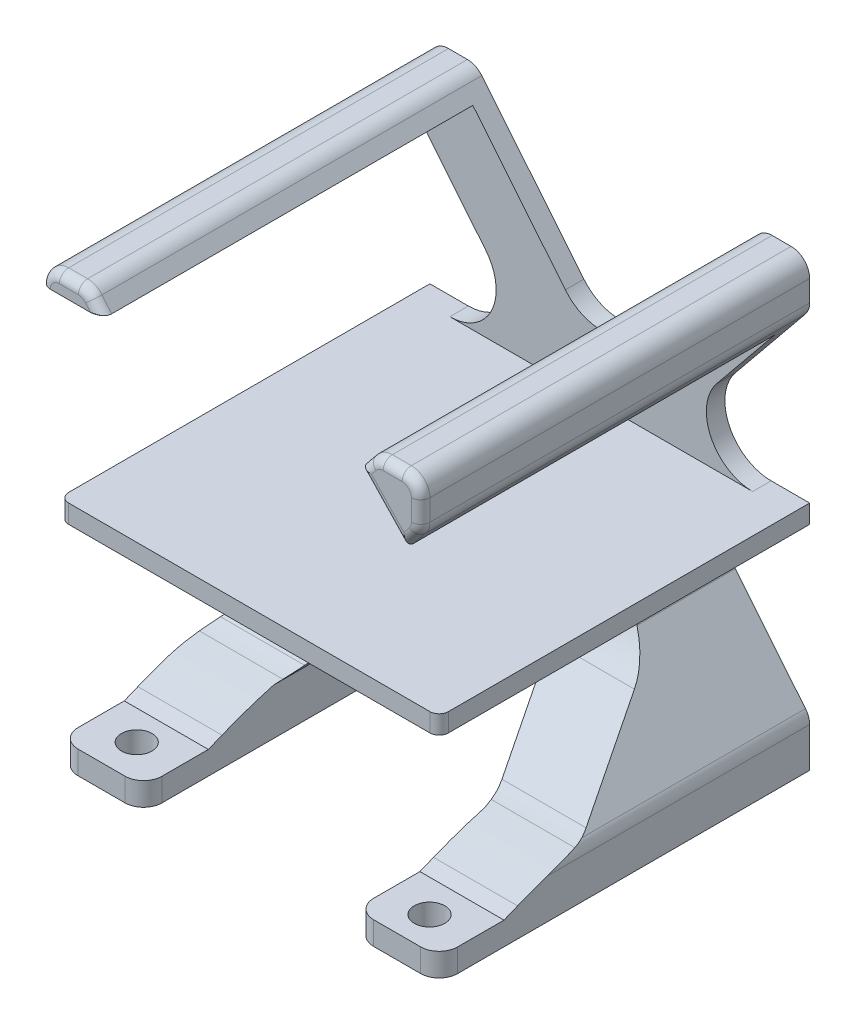
SolidWorks part; units mm, degrees
ref_plane "Front Plane" through (0, 0, 0) normal (0, 0, 1) x (1, 0, 0)
ref_plane "Top Plane" through (0, 0, 0) normal (0, 1, 0) x (1, 0, 0)
ref_plane "Right Plane" through (0, 0, 0) normal (1, 0, 0) x (0, 0, -1)
sketch "Sketch1" plane through (0, 0, 0) normal (0, 0, 1) x (1, 0, 0)
  line L0 (-20.5, -19) -> (-5.8158, -1)
  line L1 (-20.5, -24) -> (-15.5, -24)
  line L2 (-20.5, -24) -> (-20.5, -19)
  line L3 (-20.5, 24) -> (-15.5, 24)
  line L4 (20.5, -24) -> (20.5, -19)
  line L5 (20.5, 19) -> (20.5, 24)
  line L6 (20.5, -1) -> (20.5, 1)
  line L7 (-5.8158, 1) -> (-20.5, 19)
  line L8 (5.8158, 1) -> (20.5, 1)
  line L9 (-15.5, 24) -> (0, 5)
  line L10 (0, 5) -> (15.5, 24)
  line L11 (-20.5, -1) -> (-20.5, 1)
  line L12 (20.5, 19) -> (5.8158, 1)
  line L13 (5.8158, -1) -> (20.5, -19)
  line L14 (-20.5, 19) -> (-20.5, 24)
  line L15 (15.5, -24) -> (0, -5)
  line L16 (0, -5) -> (-15.5, -24)
  line L17 (15.5, 24) -> (20.5, 24)
  line L18 (-20.5, 1) -> (-5.8158, 1)
  line L20 (-20.5, -1) -> (-5.8158, -1)
  line L22 (15.5, -24) -> (20.5, -24)
  line L24 (5.8158, -1) -> (20.5, -1)
  point P0 (0, 0)
  point P5 (0, 0)
  dimension "D1" = 48
  dimension "D2" = 41
  dimension "D3" = 5
  dimension "D4" = 5
  dimension "D5" = 5
  dimension "D6" = 5
  dimension "D7" = 5
  dimension "D8" = 5
  dimension "D9" = 5
  dimension "D11" = 0
  dimension "D12" = 5
  dimension "D15" = 5
  dimension "D16" = 2
  dimension "D17" = 23
extrude "Boss-Extrude1" add sketch "Sketch1" along normal blind 40
sketch "Sketch2" plane through (0, 0, 40) normal (0, 0, 1) x (1, 0, 0)
  line L0 (-5.8158, 1) -> (-20.5, 1) construction
  line L1 (-18.75, 1) -> (18.75, 1)
  line L2 (-18.75, 1) -> (-18.75, 22)
  line L3 (-18.75, 22) -> (18.75, 22)
  line L4 (18.75, 1) -> (18.75, 22)
  line L5 (-15.5, 24) -> (-20.5, 24) construction
  dimension "D1" = 37.5
  dimension "D2" = 1.75
  dimension "D3" = 2
extrude "Cut-Extrude1" cut sketch "Sketch2" against normal blind 38
sketch "Sketch4" plane through (20.5, 0, 0) normal (1, 0, 0) x (0, 0, -1)
  line L0 (-40, -1) -> (0, -1) construction
  line L1 (-40, -19) -> (-10, -19)
  line L2 (-40, -19) -> (-40, -1)
  line L3 (-40, -1) -> (-10, -1)
  line L4 (-10, -19) -> (-10, -1)
  dimension "D1" = 30
extrude "Cut-Extrude2" cut sketch "Sketch4" against normal blind 100
chamfer "Chamfer1" distance 15 angle 30 2 edges at (-15.9605, -19, 10) (15.9605, -19, 10) first distance on face at (-15.9605, -19, 25) first distance on face at (15.9605, -19, 25)
fillet "Fillet1" radius 7 4 edges at (-15.9605, -19, 25) (15.9605, -19, 25) (0, -1, 10) (8.8956, -10.3397, 10)
sketch "Sketch5" plane through (0, 0, 40) normal (0, 0, 1) x (1, 0, 0)
  line L0 (-20.5, 24) -> (-20.5, 19)
  line L1 (-20.5, 19) -> (-18.75, 16.8548)
  line L2 (-18.75, 16.8548) -> (-13.8684, 22)
  line L3 (-13.8684, 22) -> (-15.5, 24)
  line L4 (-15.5, 24) -> (-20.5, 24)
  line L5 (13.8684, 22) -> (15.5, 24)
  line L6 (15.5, 24) -> (20.5, 24)
  line L7 (20.5, 24) -> (20.5, 19)
  line L8 (20.5, 19) -> (18.75, 16.8548)
  line L11 (13.8684, 22) -> (18.75, 16.8548)
extrude "Boss-Extrude3" add sketch "Sketch5" along normal blind 2
fillet "Fillet4" radius 2 6 edges at (-20.5, 19, 21) (-20.5, 24, 21) (-15.5, 24, 21) (15.5, 24, 21) (20.5, 19, 21) (20.5, 24, 21)
fillet "Fillet5" radius 1 16 edges at (19.9142, 23.4142, 42) (20.5, 20.8562, 42) (20.3841, 19.0413, 42) (19.3999, 17.6514, 42) (16.3092, 19.4274, 42) (14.3841, 22.6321, 42) (15.5918, 23.8067, 42) (17.4748, 24, 42) (-19.9142, 23.4142, 42) (-17.4748, 24, 42) (-15.5918, 23.8067, 42) (-14.3841, 22.6321, 42) (-16.3092, 19.4274, 42) (-19.3999, 17.6514, 42) (-20.3841, 19.0413, 42) (-20.5, 20.8562, 42)
fillet "Fillet6" radius 5 5 edges at (-5.8158, 1, 1) (-5.8158, -1, 8.5) (5.8158, -1, 8.5) (5.8158, 1, 1) (0, 5, 1)
fillet "Fillet7" radius 3 1 edges at (0, -5, 5.3377)
fillet "Fillet8" radius 1 2 edges at (20.5, 0, 40) (-20.5, 0, 40)
sketch "Sketch6" plane through (0, 0, 40) normal (0, 0, 1) x (1, 0, 0)
  line L0 (-15.5, -24) -> (-11.4211, -19)
  line L1 (-11.4211, -19) -> (-11.4211, -24)
  line L2 (-11.4211, -24) -> (-15.5, -24)
  line L3 (11.4211, -19) -> (15.5, -24)
  line L4 (15.5, -24) -> (11.4211, -24)
  line L5 (11.4211, -24) -> (11.4211, -19)
extrude "Boss-Extrude4" add sketch "Sketch6" against normal up to surface (40 mm away) up to face at (0, 3.9121, 0)
sketch "Sketch7" plane through (0, 0, 0) normal (0, 0, -1) x (-1, 0, 0)
  line L0 (11.4211, -19) -> (11.4211, -24) construction
  line L1 (-11.4211, -24) -> (-4.4211, -24)
  line L2 (-11.4211, -24) -> (-11.4211, -21.5)
  line L3 (-11.4211, -21.5) -> (-4.4211, -21.5)
  line L4 (11.4211, -24) -> (11.4211, -21.5)
  line L5 (4.4608, -21.5) -> (11.4211, -21.5)
  line L7 (-4.4211, -24) -> (-4.4211, -21.5)
  line L9 (4.4608, -24) -> (4.4608, -21.5)
  line L10 (4.4608, -24) -> (11.4211, -24)
  dimension "D1" = 7
  dimension "D2" = 6.9603
extrude "Boss-Extrude5" add sketch "Sketch7" against normal blind 5
sketch "Sketch8" plane through (20.5, 0, 0) normal (1, 0, 0) x (0, 0, -1)
  line L0 (-40, -21.5) -> (-33, -21.5)
  line L1 (-40, -24) -> (-40, -19) construction
  line L2 (-33, -21.5) -> (-26.8756, -19)
  line L3 (-26.8756, -19) -> (-40, -19)
  line L4 (-40, -19) -> (-40, -21.5)
  dimension "D1" = 7
extrude "Cut-Extrude3" cut sketch "Sketch8" against normal blind 100
fillet "Fillet9" radius 50 2 edges at (15.9605, -19, 26.8756) (-15.9605, -19, 26.8756)
sketch "Sketch9" plane through (0, -21.5, 0) normal (0, 1, 0) x (1, 0, 0)
  circle A0 centre (-15.9605, -36.1972) radius 1.65
  circle A1 centre (15.9605, -36.5) radius 1.65
extrude "Cut-Extrude4" cut sketch "Sketch9" against normal blind 100
sketch "Sketch10" plane through (0, -21.5, 0) normal (0, 1, 0) x (1, 0, 0)
  line L0 (4.4211, -5) -> (4.4211, 0) construction
  line L1 (-4.4608, -5) -> (-4.4608, 0) construction
  circle A0 centre (7.4211, -2.5) radius 1.65
  circle A1 centre (-7.4608, -2.5) radius 1.65
  dimension "D1" = 3
  dimension "D2" = 3
extrude "Cut-Extrude5" cut sketch "Sketch10" against normal blind 100
fillet "Fillet11" radius 2 2 edges at (-20.5, -19, 12.9788) (20.5, -19, 12.9788)
fillet "Fillet12" radius 2 4 edges at (20.5, -22.75, 40) (11.4211, -22.75, 40) (-20.5, -22.75, 40) (-11.4211, -22.75, 40)
sketch "Sketch11" plane through (0, 0, 2) normal (0, 0, 1) x (1, 0, 0)
  line L0 (-18.75, 22) -> (-18.75, 16.8548) construction
  line L1 (-18.75, 22) -> (-31.7165, 22)
  line L2 (-18.75, 22) -> (-18.75, 15.8746)
  line L3 (-18.75, 15.8746) -> (-31.7165, 15.8746)
  line L4 (-31.7165, 22) -> (-31.7165, 15.8746)
  line L6 (-31.7165, 15.8746) -> (-0.2869, 15.8746)
  line L7 (-31.7165, 15.8746) -> (-31.7165, 22)
  line L8 (-31.7165, 22) -> (-0.2869, 22)
  line L9 (-0.2869, 15.8746) -> (-0.2869, 22)
  line M1 (-3.8743, 9.7492) -> (-13.8684, 22)
  line M2 (-13.8684, 22) -> (-18.75, 22)
  line M3 (-18.75, 22) -> (-18.75, 16.8548)
  line M4 (-18.75, 16.8548) -> (-12.4731, 9.1606)
extrude "Cut-Extrude6" cut sketch "Sketch11" along normal blind 200 contours L1 L4 L3 L2 M3 | L6 M4 M1 M2 M3 region at (-25.2332, 18.9373, 2) region at (-14.8878, 18.6126, 2)
